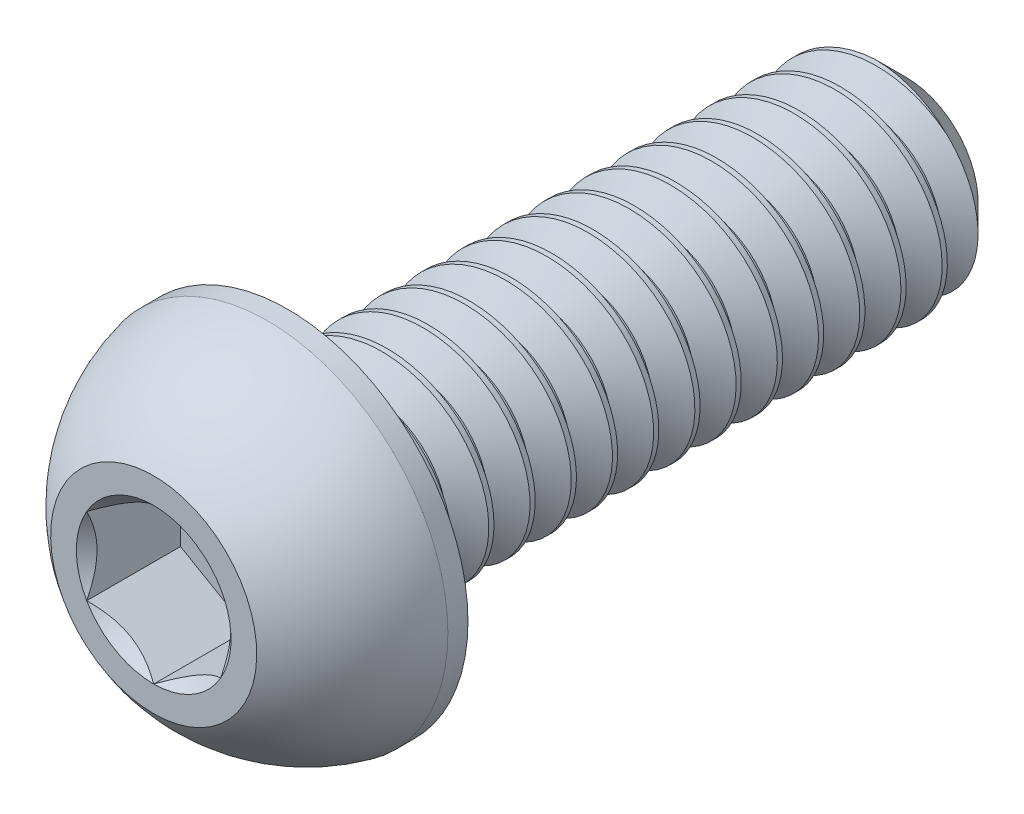
SolidWorks part; units mm, degrees
note: '?' marks a value the reader was unsure of.
ref_plane "Front" through (0, 0, 0) normal (0, 0, 1) x (1, 0, 0)
ref_plane "Top" through (0, 0, 0) normal (0, 1, 0) x (1, 0, 0)
ref_plane "Right" through (0, 0, 0) normal (1, 0, 0) x (0, 0, -1)
sketch "Sketch1" plane through (0, 0, 0) normal (1, 0, 0) x (0, 0, -1)
  line L2 (1.3, 1) -> (7.3, 1)
  line L3 (7.3, 1) -> (7.3, 0)
  line L4 (7.3, 0) -> (1.3, 0)
  line L6 (1.105, 1.75) -> (1.3, 1.75) construction
  line L7 (7.3, 1) -> (7.3, -1) construction
  line L8 (0, 0) -> (1.3, 0) construction
  line L9 (1.3, 1.75) -> (1.3, -1.75) construction
  line L11 (1.3, 1) -> (1.3, 0)
  line L13 (0, 0.65) -> (0, -0.65) construction
  line L14 (0, 0.65) -> (0, 1) construction
  arc A3 (0, 1) -> (1.105, 1.75) centre (1.4858, 0) cw construction
  dimension "D1" = 0.195
revolve "Revolve1" add sketch "Sketch1" angle 360 mid plane about L4
sketch "Sketch3" plane through (0, 0, -7.3) normal (0, 0, -1) x (-1, 0, 0)
  circle A0 centre (0, 0) radius 1
curve "Helix/Spiral1" pitch 0.4 height 6.4 turns 16
chamfer "Chamfer1" distance 0.3 angle 45 1 edges at (0, 1, -7.3)
sketch "Sketch7" plane through (0, 0, 0) normal (1, 0, 0) x (0, 0, -1)
  line L6 (1.105, 1.75) -> (1.3, 1.75) construction
  line L8 (0, 0) -> (1.3, 0) construction
  line L11 (1.3, 1.75) -> (1.3, -1.75) construction
  line L12 (1.105, 1.75) -> (1.3, 1.75)
  line L13 (0, 0) -> (1.3, 0)
  line L14 (0, 0.65) -> (0, -0.65) construction
  line L15 (1.3, 1.75) -> (1.3, 0)
  line L16 (0, 1) -> (0, 0)
  arc A2 (1.105, 1.75) -> (0, 1) centre (1.4858, 0) ccw construction
  arc A3 (1.105, 1.75) -> (0, 1) centre (1.4858, 0) ccw
revolve "Revolve2" add sketch "Sketch7" angle 360 mid plane about L13
sketch "Sketch5" plane through (0, 0, 0) normal (0, 0, 1) x (1, 0, 0)
  line L1 (0.65, -0.3753) -> (0.65, 0.3753)
  line L2 (0.65, 0.3753) -> (0, 0.7506)
  line L3 (0, 0.7506) -> (-0.65, 0.3753)
  line L4 (-0.65, 0.3753) -> (-0.65, -0.3753)
  line L5 (-0.65, -0.3753) -> (0, -0.7506)
  line L6 (0, -0.7506) -> (0.65, -0.3753)
  circle A0 centre (0, 0) radius 0.65 construction
extrude "Cut-Extrude2" cut sketch "Sketch5" against normal blind 0.91
sketch "Sketch6" plane through (0, 0, 0) normal (0, 0, 1) x (1, 0, 0)
  circle A0 centre (0, 0) radius 0.7506
extrude "Cut-Extrude3" cut sketch "Sketch6" against normal blind 0.91 draft 45
sketch "Sketch2" plane through (0, 0, 0) normal (1, 0, 0) x (0, 0, -1)
  line L0 (7, 1) -> (7.35, 1)
  line L1 (7.35, 1) -> (7.2, 0.7402)
  line L2 (7.2, 0.7402) -> (7.15, 0.7402)
  line L3 (7.15, 0.7402) -> (7, 1)
  line L4 (7.075, 0.8701) -> (7.275, 0.8701) construction
  dimension "D1" = 60
  dimension "D2" = 0.05
  dimension "D3" = 0.2
sweep "Cut-Sweep1" cut profiles "Sketch2" path "Helix/Spiral1"
sketch "Sketch10" plane through (0, 0, 0) normal (1, 0, 0) x (0, 0, -1)
  line L0 (7.3, 1) -> (7.3, -1) construction
  point P0 (6.7, -1)
  dimension "D1" = 0.6
ref_axis "Center Axis 1" through (0, 0, -8.1113) along (0, 0, 1)?
ref_plane "Contact Plane 1" through (0, 0, -1.3) normal (0, 0, -1) x (-1, 0, 0)
ref_plane "Contact Plane 2" through (0, 0, 0) normal (0, 0, 1) x (1, 0, 0)
equation "\"D3@Helix/Spiral1\" = \"Lg@Sketch1\" + \"D4@Helix/Spiral1\""
equation "\"D2@Sketch2\" = \"D4@Helix/Spiral1\" * .125"
equation "\"D3@Sketch2\" = \"D4@Helix/Spiral1\" * .5"
equation "\"D1@Chamfer1\" = \"D4@Helix/Spiral1\" * .75"
equation "\"D1@Cut-Extrude2\" = \"Head Ht@Sketch1\" * .7"
equation "\"D1@Sketch1\" = \"Head Ht@Sketch1\" * .15"
equation "\"D1@Sketch10\" = \"D4@Helix/Spiral1\" * 1.5"
equation "\"D1@Cut-Extrude3\" = \"D1@Cut-Extrude2\""
